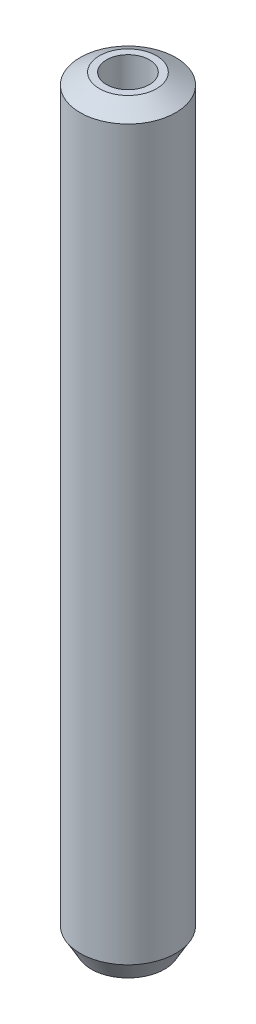
SolidWorks part; units mm, degrees
ref_plane "Front Plane" through (0, 0, 0) normal (0, 0, 1) x (1, 0, 0)
ref_plane "Top Plane" through (0, 0, 0) normal (0, 1, 0) x (1, 0, 0)
ref_plane "Right Plane" through (0, 0, 0) normal (1, 0, 0) x (0, 0, -1)
sketch "Sketch1" plane through (0, 0, 0) normal (0, 1, 0) x (1, 0, 0)
  circle A0 centre (0, 0) radius 17.5
  dimension "SHAFT_OD" = 35
extrude "Boss-Extrude1" add sketch "Sketch1" along normal blind 277.5632
sketch "Sketch2" plane through (0, 0, 0) normal (0, 1, 0) x (1, 0, 0)
  circle A0 centre (0, 0) radius 7.8601
  dimension "BORE_D" = 15.7202
extrude "Cut-Extrude1" cut sketch "Sketch2" along normal through all
chamfer "Chamfer1" distance 4.072 angle 60 2 edges at (0, 277.5632, 17.5) (0, 0, 17.5) first distance on face at (0, 277.5632, 17.5) first distance on face at (0, 0, 7.8601)
